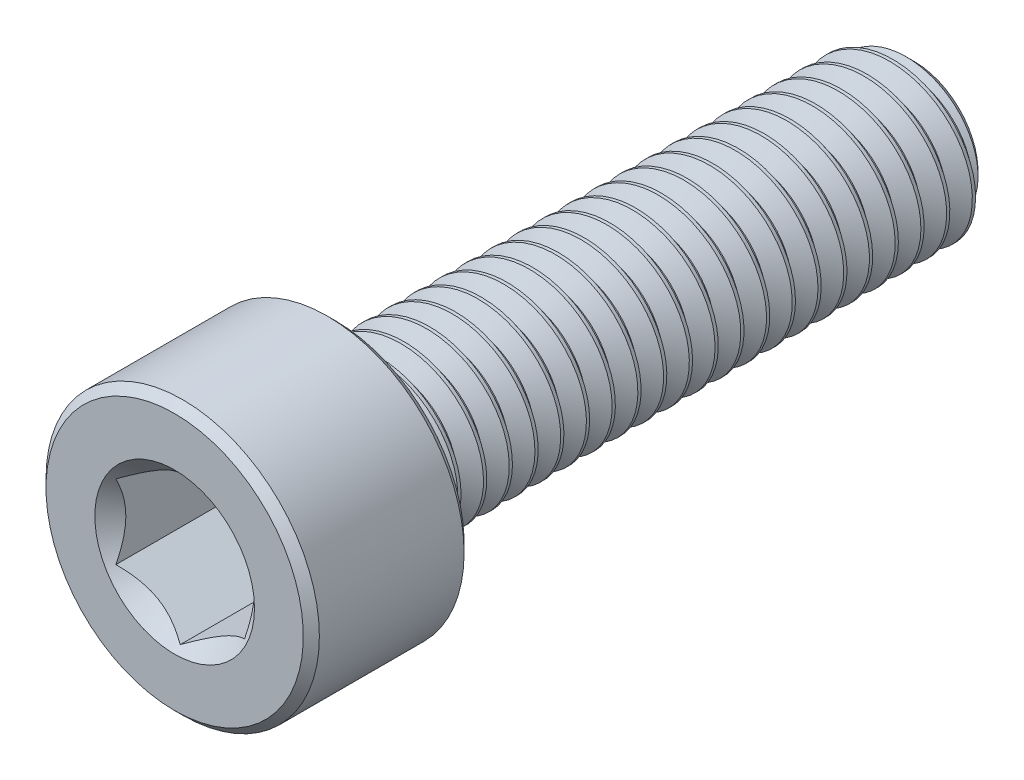
SolidWorks part; units mm, degrees
ref_plane "Front Plane" through (0, 0, 0) normal (0, 0, 1) x (1, 0, 0)
ref_plane "Top Plane" through (0, 0, 0) normal (0, 1, 0) x (1, 0, 0)
ref_plane "Right Plane" through (0, 0, 0) normal (1, 0, 0) x (0, 0, -1)
sketch "Sketch1" plane through (0, 0, 0) normal (1, 0, 0) x (0, 0, -1)
  line L0 (-11.5, 0) -> (11.5, 0) construction
  line L1 (11.5, 0) -> (11.5, 1.9804) construction
  line L2 (11.5, 1.9804) -> (10.9804, 2.5) construction
  line L3 (10.9804, 2.5) -> (10.9, 2.5) construction
  line L4 (10.9, 2.5) -> (-6.5, 2.5) construction
  line L5 (-6.5, 2.5) -> (-6.5, 4.25) construction
  line L6 (-6.5, 4.25) -> (-11.5, 4.25) construction
  line L7 (-11.5, 4.25) -> (-11.5, 0) construction
  line L8 (11.5, 1.9804) -> (11.5, 2.5) construction
  line L9 (11.45, 2.5866) -> (11.85, 1.8938) construction
  line L10 (11.85, 1.8938) -> (12.25, 2.5866) construction
  line L11 (12.25, 2.5866) -> (11.45, 2.5866) construction
  line L12 (11.85, 2.5866) -> (11.85, 2.5) construction
  line L13 (11.85, 1.8938) -> (11.85, 1.9804) construction
  line L14 (11.8, 1.9804) -> (11.9, 1.9804) construction
  line L15 (11.5, 2.5) -> (12.2, 2.5) construction
  line L16 (11.475, 2.5433) -> (12.225, 2.5433) construction
  line L17 (11.5, 0) -> (11.5, -2.5) construction
  line L18 (-6.75, 4.25) -> (-6.5, 4) construction
  line L19 (-11.25, 4.25) -> (-11.5, 4) construction
  line L20 (-6.5, 2.5) -> (-6.5, 0) construction
  line L21 (-6.5, 1.25) -> (-0.5, 1.25) construction
  line L22 (-0.5, 1.25) -> (5.5, 1.25) construction
  line L23 (5.5, 1.25) -> (11.5, 1.25) construction
  line L24 (-0.5, 1.25) -> (-0.5, 2.5) construction
  line L25 (-0.5, 2.5) -> (-0.5, 4.25) construction
  line L26 (5.5, 1.25) -> (5.5, 4.25) construction
  point P0 (-11.5, 2)
  point P3 (9.5, 2.5)
  point P4 (0, 0)
  point P18 (5.5, 2.5)
  point P22 (11.85, 1.9804)
  point P24 (10.9, 2.5)
  point P25 (11.85, 2.5)
  point P28 (11.85, 2.5433)
  point P29 (9.5, -2.5)
  point P30 (-0.5, 2.5)
  point P31 (-9, 4.25)
  point P37 (-7.375, 4.25)
  point P38 (-11.125, 4.25)
  point P45 (-0.5, 1.25)
  point P46 (5.5, 1.25)
  dimension "D2" = 0.1
  dimension "D7" = 0.25
  dimension "D8" = 0.25
  dimension "D9" = 0.25
  dimension "D10" = 0.125
  dimension "D11" = 0.625
  dimension "Drive Size" = 4
  dimension "Head Diameter" = 8.5
  dimension "Head Height" = 5
  dimension "Thread Pitch" = 0.8
  dimension "Thread Dia" = 5
  dimension "Length" = 18
  dimension "D12" = 0.6
  dimension "D4" = 2
  dimension "D3" = 45
sketch "Sketch2" plane through (0, 0, 0) normal (1, 0, 0) x (0, 0, -1)
  line L0 (-11.5, 0) -> (-11.5, 4)
  line L1 (-11.25, 4.25) -> (-6.75, 4.25)
  line L2 (-6.5, 4) -> (-6.5, 2.75)
  line L4 (10.9804, 2.5) -> (11.5, 1.9804)
  line L5 (11.5, 1.9804) -> (11.5, 0)
  line L6 (-6.5, 4.25) -> (-11.5, 4.25) construction
  line L7 (11.5, 0) -> (-11.5, 0)
  line L8 (-11.25, 4.25) -> (-11.5, 4) construction
  line L10 (-11.25, 4.25) -> (-11.5, 4)
  line L14 (-6.75, 4.25) -> (-6.5, 4) construction
  line L16 (-6.75, 4.25) -> (-6.5, 4)
  line L17 (-6.5, 2.5) -> (-6.5, 4.25) construction
  line L19 (-6.25, 2.5) -> (10.9804, 2.5)
  line L20 (10.9, 2.5) -> (-6.5, 2.5) construction
  arc A1 (-6.5, 2.75) -> (-6.25, 2.5) centre (-6.25, 2.75) ccw
  dimension "D3" = 0.25
revolve "Revolve1" add sketch "Sketch2" angle 360 about L7
sketch "Sketch3" plane through (0, 0, 11.5) normal (0, 0, 1) x (1, 0, 0)
  line L1 (2, -1.1547) -> (2, 1.1547)
  line L2 (2, 1.1547) -> (0, 2.3094)
  line L3 (0, 2.3094) -> (-2, 1.1547)
  line L4 (-2, 1.1547) -> (-2, -1.1547)
  line L5 (-2, -1.1547) -> (0, -2.3094)
  line L6 (0, -2.3094) -> (2, -1.1547)
  circle A0 centre (0, 0) radius 2 construction
  circle A1 centre (0, 0) radius 4.25 construction
  circle A2 centre (0, 0) radius 4.25 construction
  circle A3 centre (0, 0) radius 2.3094 construction
  point P13 (0, 0)
  dimension "D1" = 4.6188
extrude "Cut-Extrude1" cut sketch "Sketch3" against normal offset from surface (4 mm away) 1 up to face at (0, 4, 6.5)
sketch "Sketch4" plane through (0, 0, 11.5) normal (0, 0, 1) x (1, 0, 0)
  circle A0 centre (0, 0) radius 2.4826
  dimension "D1" = 4.9652
extrude "Cut-Extrude2" cut sketch "Sketch4" against normal up to vertex (2.5 mm away) draft 45 up to point (0, 4.25, 9)
sketch "Sketch11" plane through (0, 0, 0) normal (1, 0, 0) x (0, 0, -1)
  line L0 (-11.5, 0) -> (11.5, 0) construction
  line L1 (-11.5, 0) -> (11.5, 0) construction
  line L2 (-3.125, 0) -> (-3.125, 2.5) construction
  line L3 (10.9, 2.5) -> (-6.5, 2.5) construction
  line L4 (8.125, 0) -> (8.125, 2.5) construction
  line L6 (11.5, 1.9804) -> (11.5, 2.5) construction
  point P2 (-3.125, 0)
  point P3 (8.125, 0)
  dimension "D1" = 3.375
  dimension "D2" = 3.375
sketch "Sketch6" plane through (0, 0, -11.5) normal (0, 0, -1) x (-1, 0, 0)
  circle A0 centre (0, 0) radius 2.5
curve "Helix/Spiral1" pitch 0.8 height 18.8 radius 2.5 centre (0, 0, -11.5) axis (0, 0, 1) start towards (0, 1, 0)
sketch "Sketch10" plane through (0, 0, 0) normal (1, 0, 0) x (0, 0, -1)
  line L0 (-6.25, -4.25) -> (-6.25, 4.25)
  line L5 (-11.5, 0) -> (11.5, 0) construction
  line L6 (-6.25, 2.5) -> (-6.25, -2.5) construction
  point P3 (-6.25, 0)
split "Split1" trim tools "Sketch10" bodies to split 106 resulting bodies 114 115
sketch "Sketch7" plane through (0, 0, 0) normal (1, 0, 0) x (0, 0, -1)
  line L0 (11.475, 2.5433) -> (12.225, 2.5433)
  line L1 (12.225, 2.5433) -> (11.9, 1.9804)
  line L2 (11.9, 1.9804) -> (11.8, 1.9804)
  line L3 (11.8, 1.9804) -> (11.475, 2.5433)
sweep "Cut-Sweep1" cut profiles "Sketch7" path "Helix/Spiral1" align with end faces yes
sketch "Sketch8" plane through (0, 0, 0) normal (1, 0, 0) x (0, 0, -1)
  line L0 (-6.5, 0) -> (-6.5, 2.5)
  line L1 (-6.25, -2.5) -> (-6.25, 2.5) construction
  line L2 (-6.5, 2.5) -> (-6.25, 2.5)
  line L4 (-6.25, 2.5) -> (-4.8066, 0)
  line L5 (-4.8066, 0) -> (-6.5, 0)
  line L6 (10.9, 2.5) -> (-6.5, 2.5) construction
  line L7 (-11.5, 0) -> (11.5, 0) construction
  dimension "D1" = 60
revolve "Revolve2" add sketch "Sketch8" angle 360 about L5
equation "\"D2@Sketch1\" = \"Thread Pitch@Sketch1\" / 8"
equation "\"D4@Helix/Spiral1\" = \"Thread Pitch@Sketch1\""
equation "\"D7@Sketch1\" = \"Head Height@Sketch1\" * .05"
equation "\"D8@Sketch1\"=\"D7@Sketch1\""
equation "\"D9@Sketch1\"=\"D7@Sketch1\""
equation "\"D10@Sketch1\"=\"D7@Sketch1\"/2"
equation "\"D11@Sketch1\"=\"D10@Sketch1\"*5"
equation "\"D4@Sketch1\"=\"Thread Pitch@Sketch1\"*2.5"
equation "\"D12@Sketch1\"=\"Thread Pitch@Sketch1\"*.75"
equation "\"D3@Helix/Spiral1\"=\"Length@Sketch1\"+\"Thread Pitch@Sketch1\""
equation "\"D3@Sketch2\"=\"Thread Dia@Sketch1\"*0.05"
equation "\"D1@Sketch11\"=\"Length@Sketch1\"*0.1875"
equation "\"D2@Sketch11\"=\"D1@Sketch11\""
equation "\"D1@Sketch4\"=\"D1@Sketch3\"*1.075"
